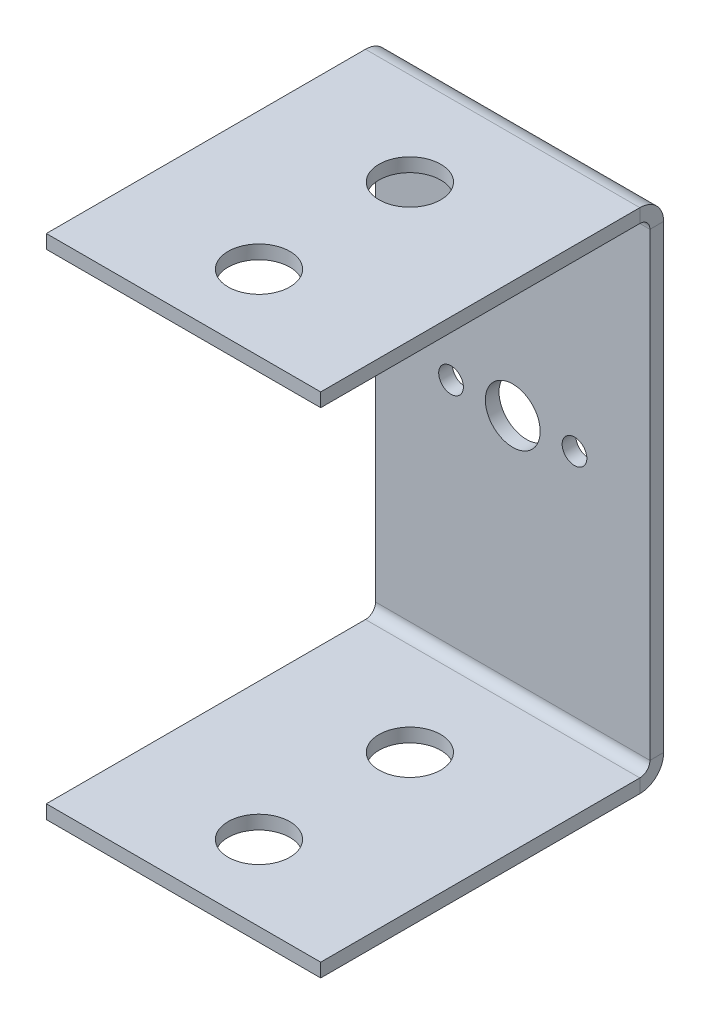
SolidWorks part; units mm, degrees
note: The reader was unsure of these and kept them because the rebuilt part matched: flange length of "Edge-Flange1".
material "5052-H34"
ref_plane "Front Plane" through (0, 0, 0) normal (0, 0, 1) x (1, 0, 0)
ref_plane "Top Plane" through (0, 0, 0) normal (0, 1, 0) x (1, 0, 0)
ref_plane "Right Plane" through (0, 0, 0) normal (1, 0, 0) x (0, 0, -1)
sketch "Sketch1" plane through (0, 0, 0) normal (0, 0, 1) x (1, 0, 0)
  line L1 (-10, 18.5) -> (10, 18.5)
  line L2 (-10, 18.5) -> (-10, -18.5)
  line L3 (-10, -18.5) -> (10, -18.5)
  line L4 (10, 18.5) -> (10, -18.5)
  line L5 (-10, 18.5) -> (10, -18.5) construction
  line L6 (-10, -18.5) -> (10, 18.5) construction
  point P0 (0, 0)
  dimension "D1" = 37
  dimension "D2" = 20
base flange "Base-Flange1" sketch "Sketch1" thickness 1 reverse thickness direction no parameters "D1"=0.7366
edge flange "Edge-Flange1" sketch "Sketch8" flange angle 90 flange length 24 flange position material inside bend radius 0.7366 thickness 1 relief rectangular parameters "D6"=10
sketch "Sketch8" plane through (0, 18.5, 0) normal (0, 1, 0) x (-1, 0, 0)
  line L0 (-10, 0) -> (10, 0) construction
  line L1 (-10, 0) -> (10, 0)
  line L2 (-10, 0) -> (-10, 24)
  line L3 (-10, 24) -> (10, 24)
  line L4 (10, 24) -> (10, 0)
bend "EdgeBend1" bend radius 0.7366 bend angle 90 parameters "D5"=1
mirror "Mirror1" about plane through (0, 0, 0) normal (0, 1, 0) of "Edge-Flange1"
bend "MirrorBend1" bend radius 0.7366 bend angle 90 parameters "D5"=2
sketch "Sketch9" plane through (0, 0, -1) normal (0, 0, -1) x (-1, 0, 0)
  line L0 (-4.5, 0) -> (4.5, 0) construction
  line L1 (11, 0) -> (-11, 0) construction
  circle A0 centre (0, 0) radius 2
  circle A1 centre (-4.5, 0) radius 0.9
  circle A2 centre (4.5, 0) radius 0.9
  point P8 (0, 0)
  dimension "D1" = 4
  dimension "D3" = 1.8
  dimension "D4" = 1.8
  dimension "D2" = 9
extrude "Cut-Extrude1" cut sketch "Sketch9" against normal blind 10 normal cut yes
sketch "Sketch10" plane through (0, 18.5, 0) normal (0, 1, 0) x (1, 0, 0)
  line L0 (0, -7.5) -> (0, -18.5) construction
  line L1 (-11, -13) -> (11, -13) construction
  circle A0 centre (0, -7.5) radius 2.25
  circle A1 centre (0, -18.5) radius 2.25
  point P5 (0, -13)
  dimension "D2" = 4.5
  dimension "D1" = 11
extrude "Cut-Extrude2" cut sketch "Sketch10" against normal through all normal cut yes
sketch "Bend-Lines1" [suppressed] plane through (0, 0, 0) normal (0, 1, 0) x (1, 0, 0)
sketch "Bounding-Box1" [suppressed] plane through (0, 0, 0) normal (0, 1, 0) x (1, 0, 0)
sheet metal parameters "Sheet-Metal1" thickness 1 parameters "D1"=0.7366
flat pattern "Flat-Pattern1" [suppressed]
sketch "Bend-Lines2" plane through (0, 0, 0) normal (0, 1, 0) x (1, 0, 0)
sketch3d "Bounding-Box2" [suppressed]
  line L0 (-10, 18.5, 0) -> (-10, -18.5, 0) construction
  line L1 (10, 18.5, 0) -> (10, -18.5, 0) construction
  line L2 (-10, 18.5, 0) -> (10, 18.5, 0) construction
  line L3 (-10, -18.5, 0) -> (10, -18.5, 0) construction
sheet metal parameters "Sheet-Metal2" thickness 1 parameters "D1"=0.7366
flat pattern "Flat-Pattern1"
sketch "Bend-Lines2" plane through (0, 0, 0) normal (0, 0, 1) x (1, 0, 0)
  line L0 (10, 17.6561) -> (-10, 17.6561) construction
  line L1 (10, 17.6561) -> (-10, 17.6561) construction
sketch3d "Bounding-Box2" [suppressed]
  line L0 (10, 41.8122, 0) -> (10, -18.5, 0) construction
  line L1 (-10, 41.8122, 0) -> (-10, -18.5, 0) construction
  line L2 (10, 41.8122, 0) -> (-10, 41.8122, 0) construction
  line L3 (10, -18.5, 0) -> (-10, -18.5, 0) construction
bend of the flat pattern "Flatten-<EdgeBend1>1"
sheet metal parameters "Sheet-Metal3" thickness 1 parameters "D1"=0.7366
flat pattern "Flat-Pattern1"
sketch "Bend-Lines2" plane through (0, 0, 0) normal (0, 0, 1) x (1, 0, 0)
  line L0 (10, 17.6561) -> (-10, 17.6561) construction
  line L1 (10, 17.6561) -> (-10, 17.6561) construction
  line L2 (-10, -17.6561) -> (10, -17.6561) construction
  line L3 (-10, -17.6561) -> (10, -17.6561) construction
sketch3d "Bounding-Box2" [suppressed]
  line L0 (10, 41.8122, 0) -> (10, -41.8122, 0) construction
  line L1 (-10, 41.8122, 0) -> (-10, -41.8122, 0) construction
  line L2 (10, 41.8122, 0) -> (-10, 41.8122, 0) construction
  line L3 (10, -41.8122, 0) -> (-10, -41.8122, 0) construction
bend of the flat pattern "Flatten-<EdgeBend1>1"
bend of the flat pattern "Flatten-<MirrorBend1>1"
sheet metal parameters "Sheet-Metal4" thickness 1 parameters "D1"=0.7366
flat pattern "Flat-Pattern1"
sketch "Bend-Lines2" plane through (0, 0, 0) normal (0, 0, 1) x (1, 0, 0)
  line L0 (10, 17.6561) -> (-10, 17.6561) construction
  line L1 (10, 17.6561) -> (-10, 17.6561) construction
  line L2 (-10, -17.6561) -> (10, -17.6561) construction
  line L3 (-10, -17.6561) -> (10, -17.6561) construction
sketch3d "Bounding-Box2" [suppressed]
  line L0 (10, 41.8122, 0) -> (10, -41.8122, 0) construction
  line L1 (-10, 41.8122, 0) -> (-10, -41.8122, 0) construction
  line L2 (10, 41.8122, 0) -> (-10, 41.8122, 0) construction
  line L3 (10, -41.8122, 0) -> (-10, -41.8122, 0) construction
bend of the flat pattern "Flatten-<EdgeBend1>1"
bend of the flat pattern "Flatten-<MirrorBend1>1"
sheet metal parameters "Sheet-Metal5" thickness 1 parameters "D1"=0.7366
flat pattern "Flat-Pattern1"
sketch "Bend-Lines2" plane through (0, 0, 0) normal (0, 0, 1) x (1, 0, 0)
  line L0 (10, 17.6561) -> (-10, 17.6561) construction
  line L1 (10, 17.6561) -> (-10, 17.6561) construction
  line L2 (-10, -17.6561) -> (10, -17.6561) construction
  line L3 (-10, -17.6561) -> (10, -17.6561) construction
sketch3d "Bounding-Box2" [suppressed]
  line L0 (10, 41.8122, 0) -> (10, -41.8122, 0) construction
  line L1 (-10, 41.8122, 0) -> (-10, -41.8122, 0) construction
  line L2 (10, 41.8122, 0) -> (-10, 41.8122, 0) construction
  line L3 (10, -41.8122, 0) -> (-10, -41.8122, 0) construction
bend of the flat pattern "Flatten-<EdgeBend1>1"
bend of the flat pattern "Flatten-<MirrorBend1>1"
